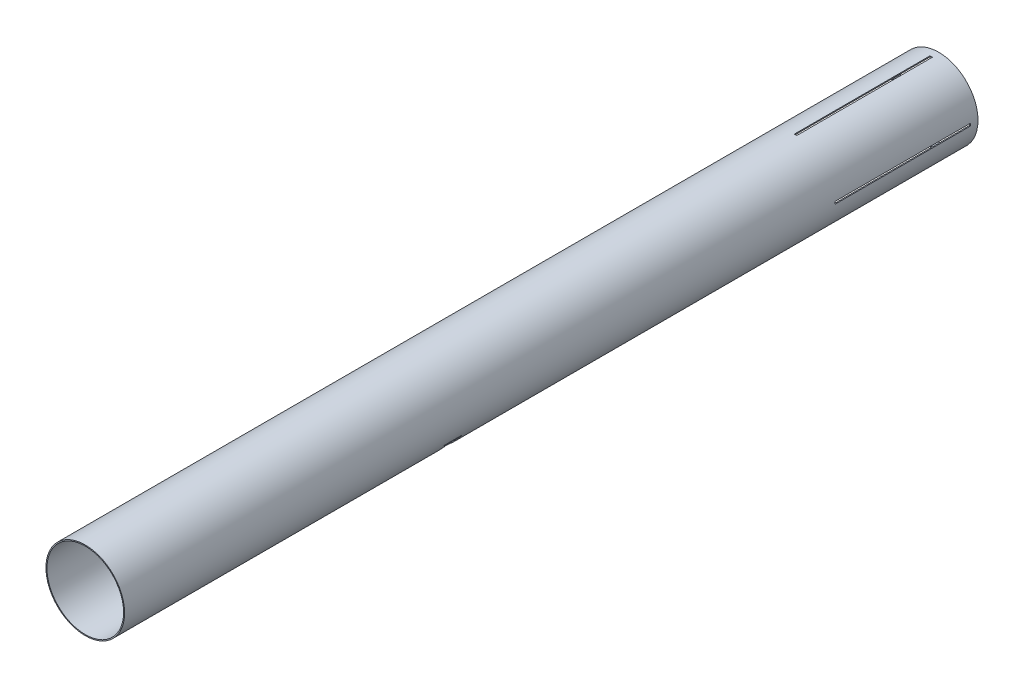
SolidWorks part; units mm, degrees
material "E-Glass Fiber"
ref_plane "Front" through (0, 0, 0) normal (0, 0, 1) x (1, 0, 0)
ref_plane "Top" through (0, 0, 0) normal (0, 1, 0) x (1, 0, 0)
ref_plane "Right" through (0, 0, 0) normal (1, 0, 0) x (0, 0, -1)
sketch "Sketch1" plane through (0, 0, 0) normal (0, 0, 1) x (1, 0, 0)
  circle A0 centre (0, 0) radius 78.35
  circle A1 centre (0, 0) radius 76.35
  dimension "D1" = 2
  dimension "D2" = 152.7
extrude "Boss-Extrude1" add sketch "Sketch1" along normal blind 1700
sketch "Sketch4" plane through (0, 0, 0) normal (0, 0, 1) x (1, 0, 0)
  line L0 (0, 0) -> (25.0476, -25.0476) construction
  line L1 (0, 0) -> (0, -24.8691) construction
  dimension "D1" = 45
ref_plane "Plane1" through (0, 0, 0) normal (0.7071, -0.7071, 0) x (0, 0, -1)
sketch "Sketch5" plane through (0, 0, 0) normal (0.7071, -0.7071, 0) x (0, 0, -1)
  line L0 (0, -78.35) -> (0, 78.35) construction
  circle A0 centre (-1034.89, 0) radius 15
  dimension "D1" = 30
  dimension "D2" = 1034.89
extrude "Cut-Extrude2" cut sketch "Sketch5" along normal through all
sketch "Sketch6" plane through (0, 0, 0) normal (0, 1, 0) x (1, 0, 0)
  line L0 (-2.4, -285) -> (-2.4, -15)
  line L1 (-2.4, -285) -> (2.4, -285)
  line L2 (-2.4, -15) -> (2.4, -15)
  line L3 (2.4, -285) -> (2.4, -15)
  line L4 (-2.4, -285) -> (2.4, -15) construction
  line L5 (-2.4, -15) -> (2.4, -285) construction
  line L6 (78.35, 0) -> (-78.35, 0) construction
  line L7 (0, 0) -> (0, -1700) construction
  line L8 (-78.35, -1700) -> (78.35, -1700) construction
  point P1 (0, -150)
  dimension "D1" = 15
  dimension "D2" = 4.8
  dimension "D3" = 270
extrude "Cut-Extrude3" cut sketch "Sketch6" against normal through all both and the other way through all
pattern_circular "CirPattern1" count 2 every 90 about axis through (0, 0, 0) along (0, 0, 1) of "Cut-Extrude3"
ref_plane "Plane2" through (0, 0, 1035) normal (0, 0, 1) x (1, 0, 0)
sketch "Sketch7" plane through (0, 0, 1035) normal (0, 0, 1) x (1, 0, 0)
  line L0 (40.7914, -66.8938) -> (39.7501, -65.1863)
  line L1 (65.3269, -39.5186) -> (67.0381, -40.5538)
  line L2 (0, 0) -> (55.5, -55.3035) construction
  line L3 (42.2165, -63.6167) -> (43.3224, -65.2832)
  line L4 (63.7661, -41.9906) -> (65.4365, -43.0905)
  arc A0 (67.0381, -40.5538) -> (40.7914, -66.8938) centre (0, 0) cw
  circle A2 centre (0, 0) radius 78.35 construction
  arc A3 (65.3269, -39.5186) -> (39.7501, -65.1863) centre (0, 0) cw
  circle A4 centre (0, 0) radius 76.35 construction
  arc A5 (43.7704, -64.9836) -> (64.9836, -43.7704) centre (0, 0) ccw construction
  dimension "D1" = 55.5
  dimension "D2" = 2
  dimension "D3" = 2
  dimension "D4" = 3
  dimension "D5" = 3
extrude "Cut-Extrude4" cut sketch "Sketch7" against normal blind 17.5 and the other way blind 17.5 contours L1 A3 L4 A0 | L3 A3 L0 A0 region at (41.5275, -65.2566, 1035) region at (65.4035, -41.2957, 1035)
